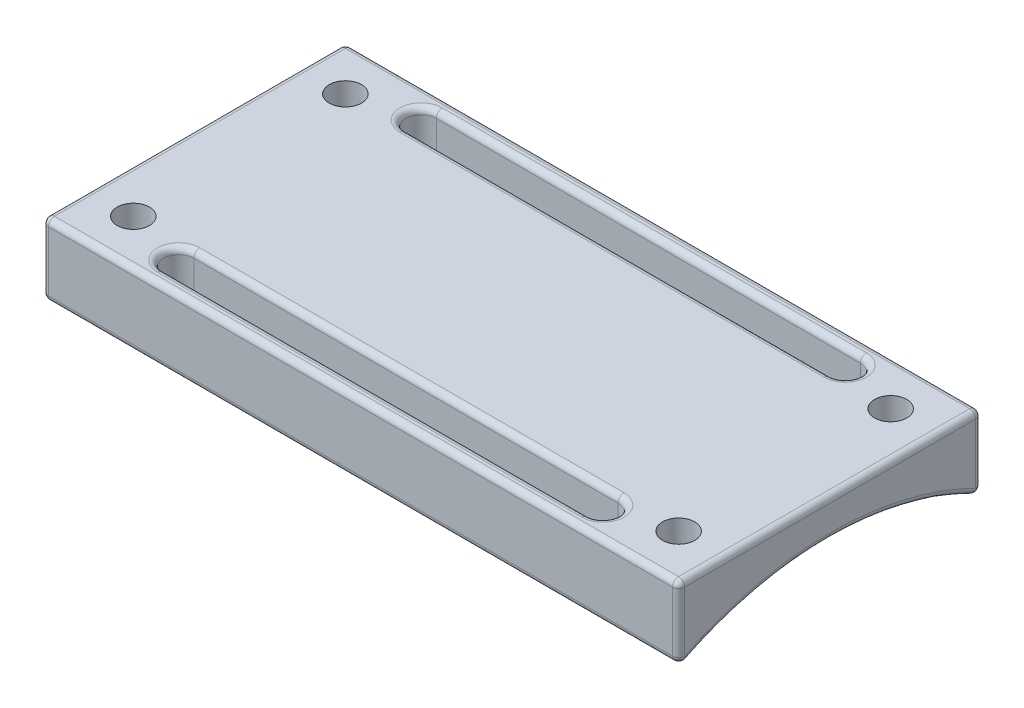
SolidWorks part; units mm, degrees
ref_plane "Front Plane" through (0, 0, 0) normal (0, 0, 1) x (1, 0, 0)
ref_plane "Top Plane" through (0, 0, 0) normal (0, 1, 0) x (1, 0, 0)
ref_plane "Right Plane" through (0, 0, 0) normal (1, 0, 0) x (0, 0, -1)
sketch "Sketch1" plane through (0, 0, 0) normal (0, 1, 0) x (1, 0, 0)
  line L1 (0, 0) -> (53.34, 0)
  line L2 (0, 0) -> (0, 25.4)
  line L3 (0, 25.4) -> (53.34, 25.4)
  line L4 (53.34, 0) -> (53.34, 25.4)
  dimension "D1" = 53.34
  dimension "D2" = 25.4
extrude "Boss-Extrude1" add sketch "Sketch1" along normal blind 6.35
sketch "Sketch3" plane through (0, 6.35, 0) normal (0, 1, 0) x (1, 0, 0)
  line L0 (0, 25.4) -> (0, 0) construction
  line L1 (53.34, 25.4) -> (0, 25.4) construction
  line L2 (53.34, 0) -> (53.34, 25.4) construction
  line L3 (0, 0) -> (53.34, 0) construction
  point P0 (3.81, 21.59)
  point P1 (49.53, 21.59)
  point P2 (3.81, 3.81)
  point P3 (49.53, 3.81)
  dimension "D1" = 3.81
  dimension "D2" = 3.81
  dimension "D3" = 3.81
  dimension "D4" = 3.81
  dimension "D5" = 3.81
  dimension "D6" = 3.81
  dimension "D7" = 3.81
  dimension "D8" = 3.81
ref_plane "Plane1" through (0, 0, 0) normal (0, 1, 0) x (1, 0, 0)
sketch "Sketch6" plane through (0, 0, 0) normal (0, 1, 0) x (1, 0, 0)
  point P0 (3.81, 21.59)
  point P2 (49.53, 21.59)
  point P4 (49.53, 3.81)
  point P6 (3.81, 3.81)
hole_wizard "CBORE for M2.5 SHCS1" positions "Sketch7" profile "Sketch8" counterbore size "M2.5" standard "ANSI Metric" end condition through all
sketch "Sketch7" plane through (0, 0, 0) normal (0, 1, 0) x (1, 0, 0)
  point P0 (3.81, 3.81)
  point P3 (3.81, 21.59)
  point P6 (49.53, 3.81)
  point P9 (49.53, 21.59)
sketch "Sketch8" plane through (3.81, 0, -3.81) normal (1, 0, 0) x (0, 0, -1)
  line L0 (0, 0) -> (0, 6.35)
  line L1 (0, 6.35) -> (1.35, 6.35)
  line L3 (1.35, 6.35) -> (1.35, 3.5)
  line L4 (1.35, 3.5) -> (3.25, 3.5)
  line L5 (3.25, 3.5) -> (3.25, 0)
  line L7 (3.25, 0) -> (0, 0)
  line L11 (0, -6.35) -> (0, 107.95) construction
  dimension "Thru Hole Dia." = 2.7
  dimension "Thru Hole Depth" = 6.35
  dimension "C'Bore Dia." = 6.5
  dimension "C'Bore Depth" = 3.5
sketch "Sketch9" plane through (0, 6.35, 0) normal (0, 1, 0) x (1, 0, 0)
  line L0 (0, 25.4) -> (0, 0) construction
  line L1 (8.89, 3.81) -> (44.45, 3.81)
  line L3 (8.89, 1.27) -> (44.45, 1.27)
  line L5 (0, 0) -> (53.34, 0) construction
  line L6 (0, 12.7) -> (4.9341, 12.7) construction
  line L9 (8.89, 24.13) -> (44.45, 24.13)
  line L10 (8.89, 21.59) -> (44.45, 21.59)
  arc A0 (44.45, 1.27) -> (44.45, 3.81) centre (44.45, 2.54) ccw
  arc A1 (8.89, 3.81) -> (8.89, 1.27) centre (8.89, 2.54) ccw
  arc A4 (8.89, 21.59) -> (8.89, 24.13) centre (8.89, 22.86) cw
  arc A5 (44.45, 24.13) -> (44.45, 21.59) centre (44.45, 22.86) cw
  dimension "D2" = 8.89
  dimension "D1" = 35.56
  dimension "D3" = 1.27
  dimension "D4" = 2.54
extrude "Cut-Extrude2" cut sketch "Sketch9" against normal blind 67.818
sketch "Sketch10" plane through (53.34, 0, 0) normal (1, 0, 0) x (0, 0, -1)
  line L0 (12.7, 0) -> (12.7, 4.1153) construction
  line L4 (0, 0) -> (25.4, 0)
  line L5 (25.4, 0) -> (25.4, 6.35)
  line L6 (25.4, 6.35) -> (0, 6.35)
  line L7 (0, 6.35) -> (0, 0)
  line L8 (0, 0) -> (25.4, 0)
  line L9 (25.4, 0) -> (25.4, 6.35)
  line L10 (25.4, 6.35) -> (0, 6.35)
  line L11 (0, 6.35) -> (0, 0)
  arc A0 (0, 0) -> (25.4, 0) centre (12.7, -23.8125) cw
  point P7 (12.7, 3.175)
  line M6 (0, 0) -> (25.4, 0)
  dimension "D2" = 3.175
  dimension "D1" = 0
extrude "Cut-Extrude3" cut sketch "Sketch10" against normal blind 482.346 contours L0 A0 M6 | L0 L8 A0 region at (53.34, 1.2766, -7.8978) region at (53.34, 1.2766, -17.5022)
fillet "Fillet3" radius 0.508 28 edges at (7.6223, 1.1586, -2.4644) (26.67, 1.6687, -3.81) (45.7185, 1.2149, -2.6027) (7.6215, 1.2149, -22.7973) (26.67, 0.635, -24.13) (45.7177, 1.1586, -22.9356) (45.72, 6.35, -2.54) (26.67, 6.35, -1.27) (7.62, 6.35, -2.54) (7.62, 6.35, -22.86) (26.67, 6.35, -24.13) (45.72, 6.35, -22.86) (0, 3.175, -25.4) (0, 6.35, -12.7) (0, 3.175, 0) (0, 3.175, -12.7) (26.67, 0.635, -1.27) (26.67, 1.6687, -21.59) (26.67, 0, -25.4) (53.34, 3.175, -12.7) (53.34, 3.175, -25.4) (53.34, 3.175, 0) (26.67, 0, 0) (26.67, 6.35, -3.81) (26.67, 6.35, -21.59) (53.34, 6.35, -12.7) (26.67, 6.35, -25.4) (26.67, 6.35, 0)
fillet "Fillet4" radius 0.254 8 edges at (49.3221, 0.3275, -24.8333) (3.6021, 0.3275, -24.8333) (49.7379, 0.3275, -0.5667) (4.0179, 0.3275, -0.5667) (49.1387, 2.574, -18.3636) (3.4187, 2.574, -18.3636) (49.2735, 0.2954, -0.5701) (3.5535, 0.2954, -0.5701)
